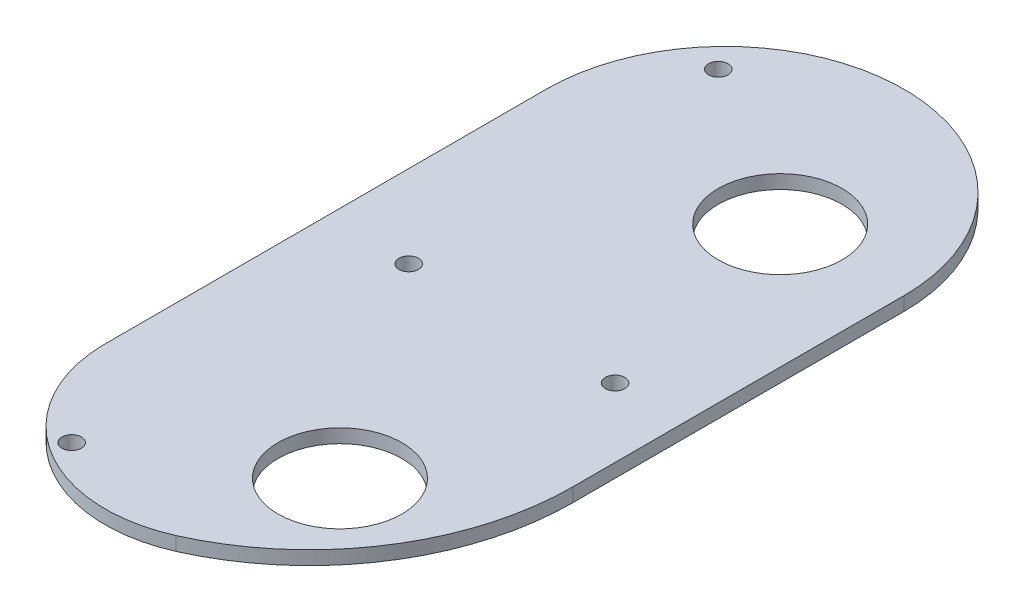
SolidWorks part; units mm, degrees
material "6061-T6 (SS)"
ref_plane "Front" through (0, 0, 0) normal (0, 0, 1) x (1, 0, 0)
ref_plane "Top" through (0, 0, 0) normal (0, 1, 0) x (1, 0, 0)
ref_plane "Right" through (0, 0, 0) normal (1, 0, 0) x (0, 0, -1)
sketch "Sketch1" plane through (0, 0, 0) normal (0, 1, 0) x (1, 0, 0)
  line L0 (0, 50.8) -> (0, -50.8) construction
  line L1 (-53.9705, 50.8) -> (-53.9705, -50.8)
  line L2 (28.5705, 50.8) -> (28.5705, -25.5942)
  circle A0 centre (0, 50.8) radius 14.2875
  circle A1 centre (0, -50.8) radius 14.2875
  circle A4 centre (0, 50.8) radius 38.1 construction
  circle A5 centre (0, -50.8) radius 38.1 construction
  arc A6 (-53.9705, -50.8) -> (-53.9587, -51.7868) centre (-12.7, -50.8) ccw
  arc A7 (-53.9705, 50.8) -> (28.5705, 50.8) centre (-12.7, 50.8) cw
  arc A8 (28.5705, -25.5942) -> (-7.5206, -81.1638) centre (-32.2555, -25.5942) cw
  arc A9 (-7.5206, -81.1638) -> (-53.9587, -51.7868) centre (-20.9482, -50.9973) cw
  point P4 (0, 0)
  point P12 (28.6545, -25.6897)
  dimension "D2" = 28.575
  dimension "D3" = 41.2705
  dimension "D4" = 76.2
  dimension "D6" = 33.02
  dimension "D7" = 60.826
  dimension "D1" = 101.6
  dimension "D5" = 12.7
extrude "Boss-Extrude1" add sketch "Sketch1" along normal blind 3.175
hole_wizard "#8 Clearance Hole1" positions "Sketch2" profile "Sketch3" hole size "#8" standard "ANSI Inch"
sketch "Sketch2" plane through (0, 3.175, 0) normal (0, 1, 0) x (1, 0, 0)
  line L6 (0, 50.8) -> (0, -50.8) construction
  line L9 (-38.1, 74.6125) -> (-38.1, -74.6125) construction
  point P2 (12.7, 0)
  point P4 (-38.1, 74.6125)
  point P10 (-38.1, -74.6125)
  point P40 (-34.925, 0)
  point P51 (-38.1, 0)
  dimension "D1" = 12.7
  dimension "D2" = 34.925
  dimension "D3" = 38.1
  dimension "D4" = 149.225
sketch "Sketch3" plane through (12.7, 3.175, 0) normal (1, 0, 0) x (0, 0, 1)
  line L0 (0, 0) -> (0, 4.5257)
  line L1 (0, 4.5257) -> (2.2479, 3.175)
  line L2 (2.2479, 3.175) -> (2.2479, 0)
  line L5 (2.2479, 0) -> (0, 0)
  line L10 (0, 4.5257) -> (-2.2479, 3.175) construction
  line L11 (0, -6.35) -> (0, 107.95) construction
  dimension "Hole Dia." = 4.4958
  dimension "Hole Depth" = 3.175
  dimension "Drill Angle" = 118
